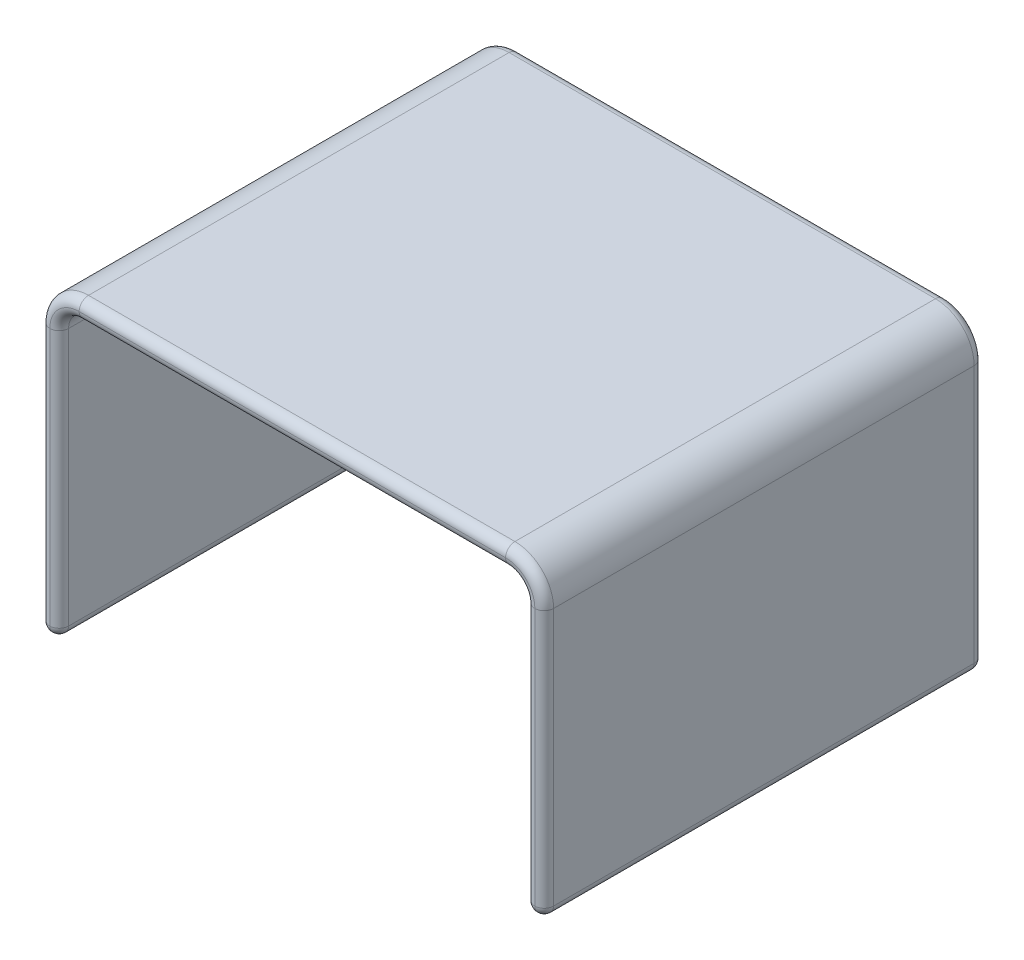
SolidWorks part; units mm, degrees
material "Plain Carbon Steel"
ref_plane "Front Plane" through (0, 0, 0) normal (0, 0, 1) x (1, 0, 0)
ref_plane "Top Plane" through (0, 0, 0) normal (0, 1, 0) x (1, 0, 0)
ref_plane "Right Plane" through (0, 0, 0) normal (1, 0, 0) x (0, 0, -1)
sketch "Sketch1" plane through (0, 0, 0) normal (0, 0, 1) x (1, 0, 0)
  line L1 (-5.461, 0.2032) -> (5.461, 0.2032)
  line L2 (-5.461, 0.2032) -> (-5.461, -0.2032)
  line L3 (-5.461, -0.2032) -> (5.461, -0.2032)
  line L4 (5.461, 0.2032) -> (5.461, -0.2032)
  line L5 (-5.461, 0.2032) -> (5.461, -0.2032) construction
  line L6 (-5.461, -0.2032) -> (5.461, 0.2032) construction
  line L7 (-5.0546, -6.4262) -> (-5.461, -6.4262)
  line L8 (-5.0546, -6.4262) -> (-5.0546, -0.2032)
  line L9 (-5.0546, -0.2032) -> (-5.461, -0.2032)
  line L10 (-5.461, -6.4262) -> (-5.461, -0.2032)
  line L11 (-5.0546, -6.4262) -> (-5.461, -0.2032) construction
  line L12 (-5.0546, -0.2032) -> (-5.461, -6.4262) construction
  line L14 (5.0546, -6.4262) -> (5.461, -6.4262)
  line L15 (5.0546, -6.4262) -> (5.0546, -0.2032)
  line L16 (5.0546, -0.2032) -> (5.461, -0.2032)
  line L17 (5.461, -6.4262) -> (5.461, -0.2032)
  line L18 (5.0546, -6.4262) -> (5.461, -0.2032) construction
  line L19 (5.0546, -0.2032) -> (5.461, -6.4262) construction
  point P0 (0, 0)
  point P5 (-5.2578, -3.3147)
  point P11 (5.2578, -3.3147)
  dimension "D1" = 0.4064
  dimension "D2" = 6.6294
  dimension "D3" = 10.922
extrude "Boss-Extrude1" add sketch "Sketch1" along normal mid plane 9.525 contours L4 L1 L2 L3 | L10 L7 L8 L3 | L14 L17 L3 L15 region at (0, 0, 0) region at (-5.2578, -3.3147, 0) region at (5.2578, -3.3147, 0)
fillet "Fillet1" radius 0.8382 2 edges at (-5.461, 0.2032, 0) (5.461, 0.2032, 0)
fillet "Fillet2" radius 0.4318 2 edges at (-5.0546, -0.2032, 0) (5.0546, -0.2032, 0)
fillet "Fillet3" radius 0.2032 24 edges at (-5.0546, -3.5306, -4.7625) (-4.9281, -0.3297, -4.7625) (0, -0.2032, -4.7625) (4.9281, -0.3297, -4.7625) (5.0546, -3.5306, -4.7625) (5.461, -3.5306, -4.7625) (5.2155, -0.0423, -4.7625) (0, 0.2032, -4.7625) (-5.2155, -0.0423, -4.7625) (-5.461, -3.5306, -4.7625) (5.2155, -0.0423, 4.7625) (5.461, -3.5306, 4.7625) (5.0546, -3.5306, 4.7625) (4.9281, -0.3297, 4.7625) (0, -0.2032, 4.7625) (-4.9281, -0.3297, 4.7625) (-5.0546, -3.5306, 4.7625) (-5.461, -3.5306, 4.7625) (-5.2155, -0.0423, 4.7625) (0, 0.2032, 4.7625) (5.0546, -6.4262, 0) (5.461, -6.4262, 0) (-5.461, -6.4262, 0) (-5.0546, -6.4262, 0)
